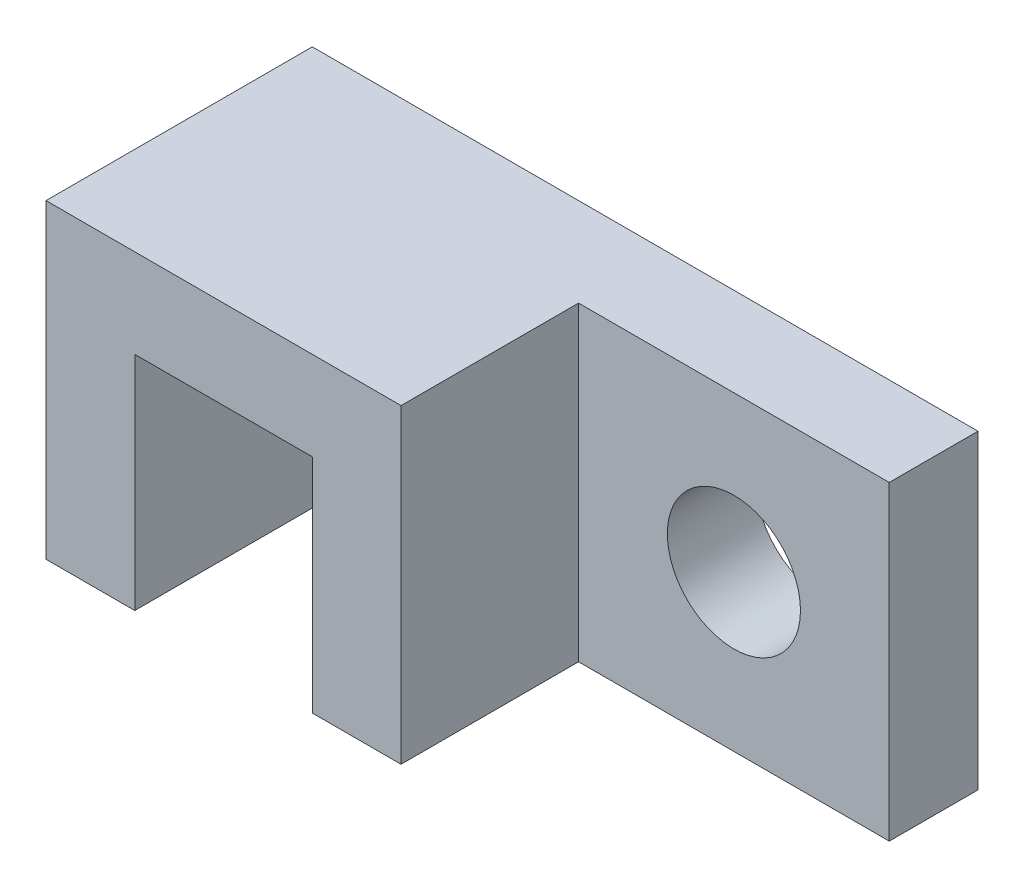
SolidWorks part; units mm, degrees
material "Plain Carbon Steel"
ref_plane "Front Plane" through (0, 0, 0) normal (0, 0, 1) x (1, 0, 0)
ref_plane "Top Plane" through (0, 0, 0) normal (0, 1, 0) x (1, 0, 0)
ref_plane "Right Plane" through (0, 0, 0) normal (1, 0, 0) x (0, 0, -1)
sketch "Sketch1" plane through (0, 0, 0) normal (0, 0, 1) x (1, 0, 0)
  line L0 (10, 0) -> (10, 25)
  line L1 (0, 0) -> (10, 0)
  line L2 (0, 0) -> (0, 35)
  line L3 (0, 35) -> (40, 35)
  line L4 (40, 0) -> (40, 35)
  line L5 (40, 35) -> (75, 35)
  line L6 (40, 35) -> (40, 0)
  line L7 (40, 0) -> (75, 0)
  line L8 (75, 35) -> (75, 0)
  line L9 (30, 0) -> (40, 0)
  line L10 (30, 0) -> (30, 25)
  line L11 (10, 25) -> (30, 25)
  line L12 (40, 0) -> (75, 35) construction
  circle A0 centre (57.5, 17.5) radius 7.5
  dimension "D5" = 15
  dimension "D2" = 35
  dimension "D3" = 40
  dimension "D4" = 35
  dimension "D6" = 10
  dimension "D7" = 10
  dimension "D1" = 10
extrude "Boss-Extrude1" add sketch "Sketch1" along normal blind 30 contours L4 L9 L10 L11 L0 L1 L2 L3
extrude "Boss-Extrude2" add sketch "Sketch1<3>" along normal blind 10 contours L4 L12 A0 L5 | L12 L7 L8 A0 region at (51.0627, 23.9373, 0) region at (63.9373, 11.0627, 0)
sketch "Sketch1<3>" plane through (0, 0, 0) normal (0, 0, 1) x (1, 0, 0) same geometry as "Sketch1"
